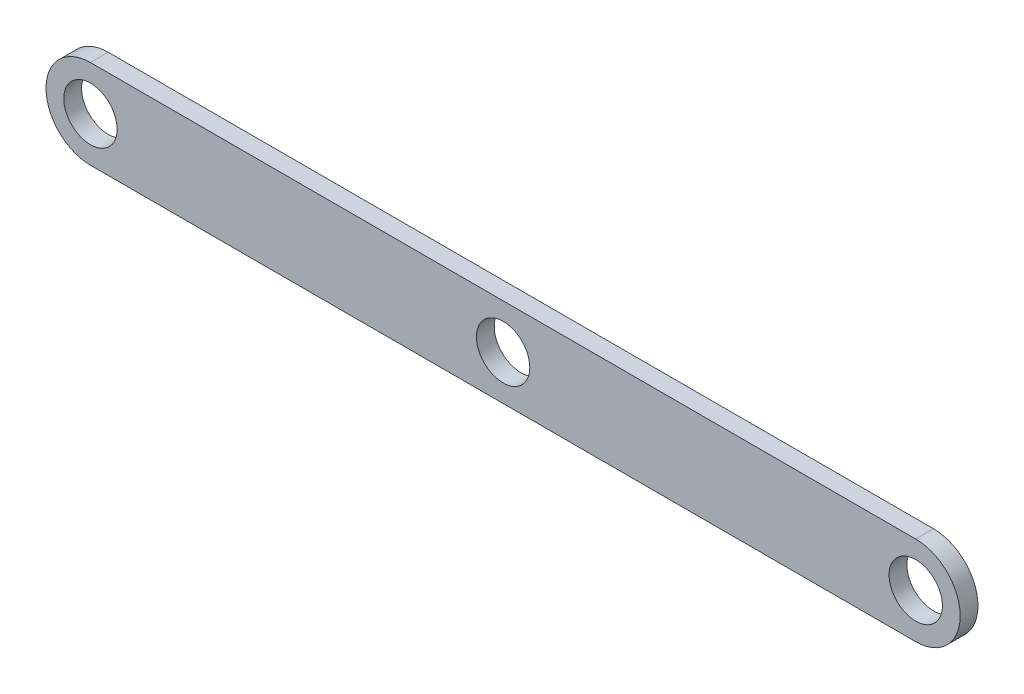
SolidWorks part; units mm, degrees
material "ALUMINUM 6061"
ref_plane "Front Plane" through (0, 0, 0) normal (0, 0, 1) x (1, 0, 0)
ref_plane "Top Plane" through (0, 0, 0) normal (0, 1, 0) x (1, 0, 0)
ref_plane "Right Plane" through (0, 0, 0) normal (1, 0, 0) x (0, 0, -1)
sketch "Sketch1" plane through (0, 0, 0) normal (0, 0, 1) x (1, 0, 0)
  line L0 (-73.66, 0) -> (73.66, 0) construction
  line L1 (-73.66, 7.9375) -> (73.66, 7.9375)
  line L2 (-73.66, -7.9375) -> (73.66, -7.9375)
  arc A0 (-73.66, 7.9375) -> (-73.66, -7.9375) centre (-73.66, 0) ccw
  arc A1 (73.66, -7.9375) -> (73.66, 7.9375) centre (73.66, 0) ccw
  circle A2 centre (73.66, 0) radius 4.7625
  circle A3 centre (-73.66, 0) radius 4.7625
  circle A4 centre (0, 0) radius 4.7625
  point P2 (0, 0)
  dimension "D3" = 9.525
  dimension "D1" = 15.875
  dimension "D2" = 147.32
extrude "Boss-Extrude1" add sketch "Sketch1" along normal blind 3.175
move or copy body "Body-Move/Copy1" [suppressed] bodies to move or copy 101
